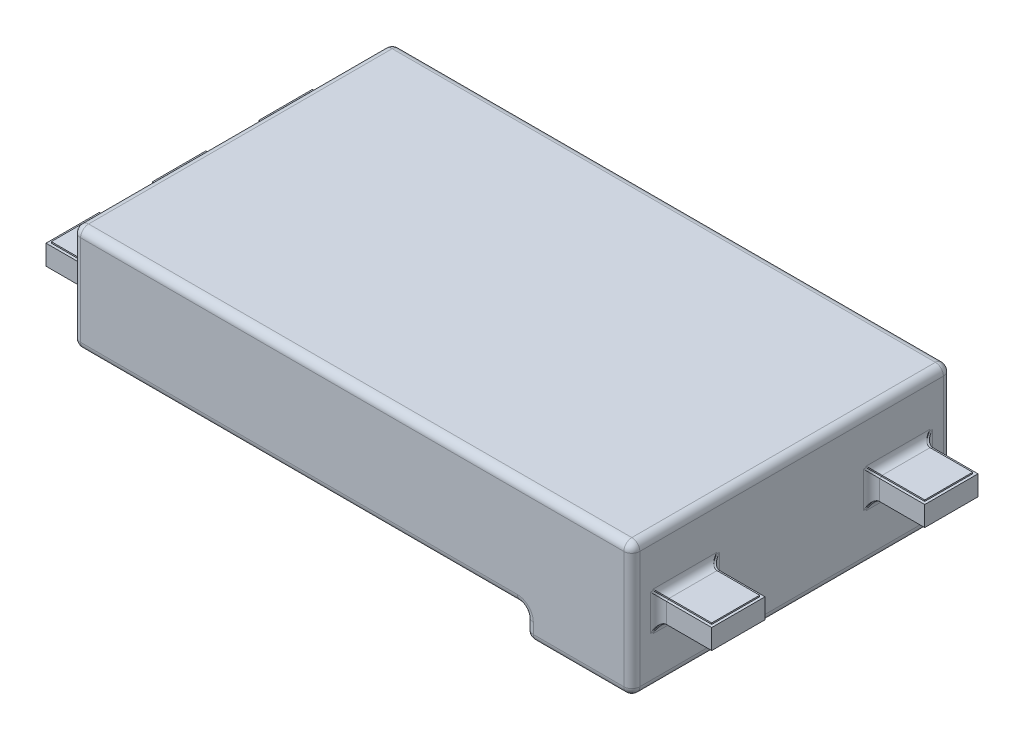
SolidWorks part; units mm, degrees
ref_plane "Front Plane" through (0, 0, 0) normal (0, 0, 1) x (1, 0, 0)
ref_plane "Top Plane" through (0, 0, 0) normal (0, 1, 0) x (1, 0, 0)
ref_plane "Right Plane" through (0, 0, 0) normal (1, 0, 0) x (0, 0, -1)
sketch "Sketch1" plane through (0, 0, 0) normal (0, 1, 0) x (1, 0, 0)
  line L1 (-10.5, 6) -> (10.5, 6)
  line L2 (-10.5, 6) -> (-10.5, -6)
  line L3 (-10.5, -6) -> (10.5, -6)
  line L4 (10.5, 6) -> (10.5, -6)
  line L5 (-10.5, 6) -> (10.5, -6) construction
  line L6 (-10.5, -6) -> (10.5, 6) construction
  point P0 (0, 0)
  dimension "D1" = 21
  dimension "D2" = 12
extrude "Boss-Extrude1" add sketch "Sketch1" along normal blind 5
sketch "Sketch2" plane through (10.5, 0, 0) normal (1, 0, 0) x (0, 0, -1)
  line L1 (0, 0) -> (0, 2.5) construction
  line L2 (4, 2.5) -> (-4, 2.5) construction
  line L4 (-5, 2.875) -> (-3, 2.875)
  line L5 (-5, 2.875) -> (-5, 2.125)
  line L6 (-5, 2.125) -> (-3, 2.125)
  line L7 (-3, 2.875) -> (-3, 2.125)
  line L8 (-5, 2.875) -> (-3, 2.125) construction
  line L9 (-5, 2.125) -> (-3, 2.875) construction
  line L10 (3, 2.875) -> (5, 2.875)
  line L11 (3, 2.875) -> (3, 2.125)
  line L12 (3, 2.125) -> (5, 2.125)
  line L13 (5, 2.875) -> (5, 2.125)
  line L14 (3, 2.875) -> (5, 2.125) construction
  line L15 (3, 2.125) -> (5, 2.875) construction
  point P6 (0, 2.5)
  dimension "D1" = 2.5
  dimension "D2" = 8
  dimension "D3" = 0.75
  dimension "D4" = 0.75
  dimension "D5" = 2
  dimension "D6" = 2
extrude "Boss-Extrude2" add sketch "Sketch2" along normal blind 2
sketch "Sketch3" plane through (-10.5, 0, 0) normal (-1, 0, 0) x (0, 0, 1)
  line L0 (0, 0) -> (0, 2.5) construction
  line L1 (4, 2.5) -> (-4, 2.5) construction
  line L3 (-1, 2.875) -> (1, 2.875)
  line L4 (-1, 2.875) -> (-1, 2.125)
  line L5 (-1, 2.125) -> (1, 2.125)
  line L6 (1, 2.875) -> (1, 2.125)
  line L7 (-1, 2.875) -> (1, 2.125) construction
  line L8 (-1, 2.125) -> (1, 2.875) construction
  line L9 (-5, 2.875) -> (-3, 2.875)
  line L10 (-5, 2.875) -> (-5, 2.125)
  line L11 (-5, 2.125) -> (-3, 2.125)
  line L12 (-3, 2.875) -> (-3, 2.125)
  line L13 (-5, 2.875) -> (-3, 2.125) construction
  line L14 (-5, 2.125) -> (-3, 2.875) construction
  line L15 (3, 2.875) -> (5, 2.875)
  line L16 (3, 2.875) -> (3, 2.125)
  line L17 (3, 2.125) -> (5, 2.125)
  line L18 (5, 2.875) -> (5, 2.125)
  line L19 (3, 2.875) -> (5, 2.125) construction
  line L20 (3, 2.125) -> (5, 2.875) construction
  point P6 (0, 2.5)
  dimension "D1" = 2.5
  dimension "D2" = 8
  dimension "D3" = 2
  dimension "D4" = 2
  dimension "D5" = 2
  dimension "D6" = 0.75
  dimension "D7" = 0.75
  dimension "D8" = 0.75
extrude "Boss-Extrude3" add sketch "Sketch3" along normal blind 2
sketch "Sketch5" plane through (0, 2.875, 0) normal (0, 1, 0) x (1, 0, 0)
  line L0 (0, 0) -> (-10.5, 0) construction
  line L1 (-10.5, -1) -> (-10.5, 1) construction
  line L3 (-10.5, 0) -> (-11.5, 0) construction
  line L4 (-10.5, 0.9) -> (-10.5, -0.9)
  line L5 (-10.5, 0.9) -> (-12.4, 0.9)
  line L6 (-10.5, -0.9) -> (-12.4, -0.9)
  line L7 (-12.4, 0.9) -> (-12.4, -0.9)
  line L8 (-10.5, 3) -> (-10.5, 5) construction
  line L9 (-10.5, 4.9) -> (-12.4, 4.9)
  line L10 (-10.5, 4.9) -> (-10.5, 3.1)
  line L11 (-10.5, 3.1) -> (-12.4, 3.1)
  line L12 (-12.4, 4.9) -> (-12.4, 3.1)
  line L13 (-10.5, 6) -> (-10.5, -6) construction
  line L14 (-10.5, -3.1) -> (-12.4, -3.1)
  line L15 (-10.5, -3.1) -> (-10.5, -4.9)
  line L16 (-10.5, -4.9) -> (-12.4, -4.9)
  line L17 (-12.4, -3.1) -> (-12.4, -4.9)
  line L18 (-12.5, 3) -> (-10.5, 3) construction
  line L19 (-12.5, -3) -> (-10.5, -3) construction
  line L20 (10.5, -6) -> (10.5, 6) construction
  line L21 (10.5, 4.9) -> (12.4, 4.9)
  line L22 (10.5, 4.9) -> (10.5, 3.1)
  line L23 (10.5, 3.1) -> (12.4, 3.1)
  line L24 (12.4, 4.9) -> (12.4, 3.1)
  line L25 (12.5, -3) -> (10.5, -3) construction
  line L26 (10.5, -3.1) -> (12.4, -3.1)
  line L27 (10.5, -3.1) -> (10.5, -4.9)
  line L28 (10.5, -4.9) -> (12.4, -4.9)
  line L29 (12.4, -3.1) -> (12.4, -4.9)
  line L30 (12.5, 3) -> (10.5, 3) construction
  dimension "D1" = 1
  dimension "D2" = 1.8
  dimension "D3" = 1.9
  dimension "D4" = 0.9
  dimension "D5" = 1.9
  dimension "D6" = 1.8
  dimension "D7" = 1.8
  dimension "D8" = 1.9
  dimension "D9" = 0.1
  dimension "D10" = 0.1
  dimension "D11" = 1.9
  dimension "D12" = 1.9
  dimension "D13" = 0.1
  dimension "D14" = 1.8
  dimension "D15" = 1.8
  dimension "D16" = 0.1
extrude "Boss-Extrude4" add sketch "Sketch5" along normal blind 0.05
ref_plane "Plane1" through (0, 2.5, 0) normal (0, 1, 0) x (1, 0, 0)
mirror "Mirror1" about plane through (0, 2.5, 0) normal (0, 1, 0) of "Boss-Extrude4"
sketch "Sketch6" plane through (0, 0, -6) normal (0, 0, -1) x (-1, 0, 0)
  line L0 (-10.5, 0) -> (10.5, 0) construction
  line L1 (-6.5, 0) -> (10.5, 0)
  line L2 (-6.5, 0) -> (-6.5, 1)
  line L3 (-6.5, 1) -> (10.5, 1)
  line L4 (10.5, 0) -> (10.5, 1)
  line L5 (10.5, 5) -> (10.5, 0) construction
  dimension "D1" = 1
  dimension "D2" = 17
extrude "Cut-Extrude1" cut sketch "Sketch6" against normal up to next
fillet "Fillet1" radius 0.3 4 edges at (0, 5, 6) (-10.5, 5, 0) (0, 5, -6) (10.5, 5, 0)
fillet "Fillet2" radius 0.3 78 edges at (-10.4121, 4.9121, -5.9121) (-10.4121, 4.9121, 5.9121) (10.4121, 4.9121, 5.9121) (10.4121, 4.9121, -5.9121) (6.5, 0, 0) (6.5, 1, 0) (8.5, 0, 6) (6.5, 0.5, 6) (-2, 1, 6) (-2, 1, -6) (6.5, 0.5, -6) (8.5, 0, -6) (-10.5, 1, 0) (-10.5, 2.85, -6) (-10.5, 2.85, 6) (-10.5, 2.1, 0.9) (-10.5, 2.125, 0.95) (-10.5, 2.5, 1) (-10.5, 2.875, 0.95) (-10.5, 2.9, 0.9) (-10.5, 2.925, 0) (-10.5, 2.9, -0.9) (-10.5, 2.875, -0.95) (-10.5, 2.5, -1) (-10.5, 2.125, -0.95) (-10.5, 2.1, -0.9) (-10.5, 2.075, 0) (-10.5, 2.5, -3) (-10.5, 2.875, -3.05) (-10.5, 2.9, -3.1) (-10.5, 2.925, -4) (-10.5, 2.9, -4.9) (-10.5, 2.875, -4.95) (-10.5, 2.5, -5) (-10.5, 2.125, -4.95) (-10.5, 2.1, -4.9) (-10.5, 2.075, -4) (-10.5, 2.1, -3.1) (-10.5, 2.125, -3.05) (-10.5, 2.5, 5) (-10.5, 2.875, 4.95) (-10.5, 2.9, 4.9) (-10.5, 2.925, 4) (-10.5, 2.9, 3.1) (-10.5, 2.875, 3.05) (-10.5, 2.5, 3) (-10.5, 2.125, 3.05) (-10.5, 2.1, 3.1) (-10.5, 2.075, 4) (-10.5, 2.1, 4.9) (-10.5, 2.125, 4.95) (10.5, 0, 0) (10.5, 2.35, 6) (10.5, 2.35, -6) (10.5, 2.5, -5) (10.5, 2.875, -4.95) (10.5, 2.9, -4.9) (10.5, 2.925, -4) (10.5, 2.9, -3.1) (10.5, 2.875, -3.05) (10.5, 2.5, -3) (10.5, 2.125, -3.05) (10.5, 2.1, -3.1) (10.5, 2.075, -4) (10.5, 2.1, -4.9) (10.5, 2.125, -4.95) (10.5, 2.5, 3) (10.5, 2.875, 3.05) (10.5, 2.9, 3.1) (10.5, 2.925, 4) (10.5, 2.9, 4.9) (10.5, 2.875, 4.95) (10.5, 2.5, 5) (10.5, 2.125, 4.95) (10.5, 2.1, 4.9) (10.5, 2.075, 4) (10.5, 2.1, 3.1) (10.5, 2.125, 3.05)
sketch "Sketch7" plane through (0, 5, 0) normal (0, 1, 0) x (1, 0, 0)
  line L0 (-190.5478, -374.8912) -> (-988.5478, -374.8912) construction
